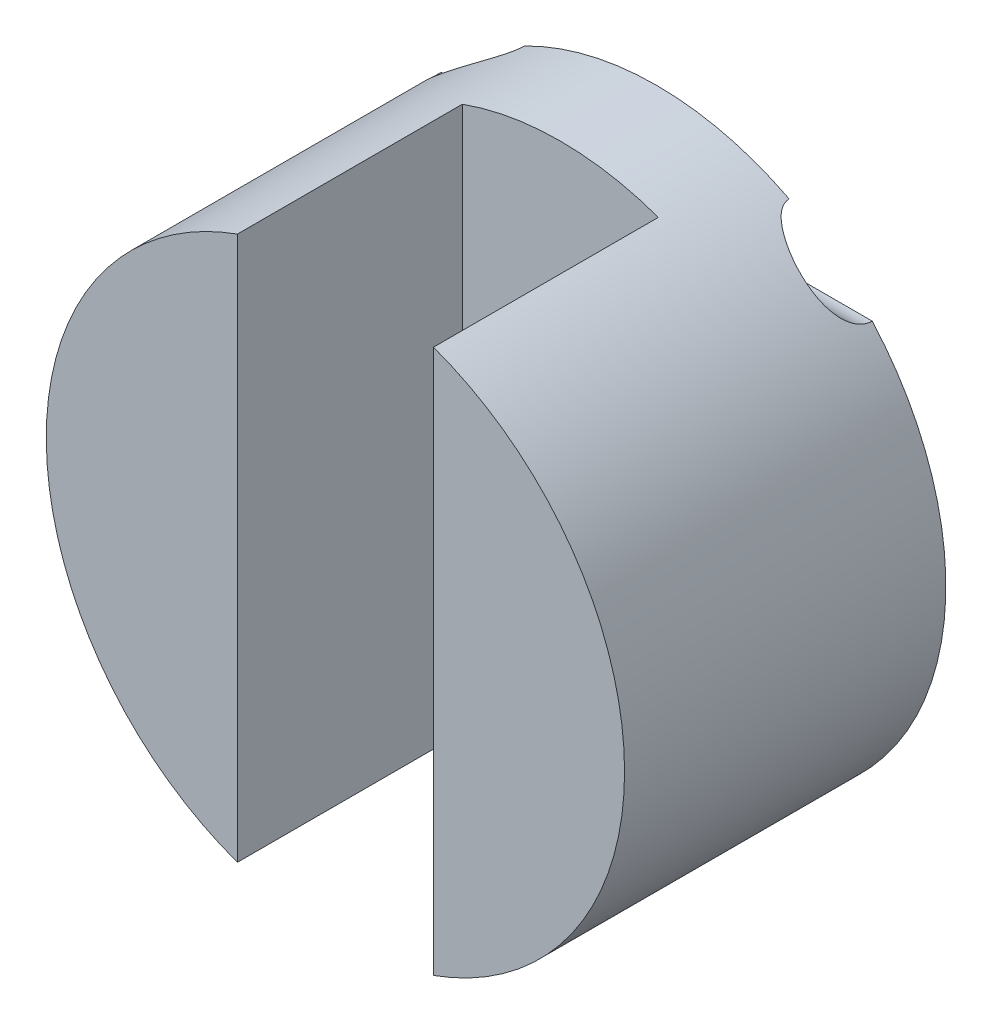
SolidWorks part; units mm, degrees
ref_plane "前视基准面" through (0, 0, 0) normal (0, 0, 1) x (1, 0, 0)
ref_plane "上视基准面" through (0, 0, 0) normal (0, 1, 0) x (1, 0, 0)
ref_plane "右视基准面" through (0, 0, 0) normal (1, 0, 0) x (0, 0, -1)
other "Configuration Table"
sketch "Sketch1" plane through (0, 0, 0) normal (0, 0, 1) x (1, 0, 0)
  circle A0 centre (0, 0) radius 90
extrude "Boss-Extrude1" add sketch "Sketch1" along normal blind 100
sketch "Sketch2" plane through (0, 0, 0) normal (0, 1, 0) x (1, 0, 0)
  line L1 (-30.5, -100) -> (30.5, -100)
  line L2 (-30.5, -100) -> (-30.5, -30)
  line L3 (-30.5, -30) -> (30.5, -30)
  line L4 (30.5, -100) -> (30.5, -30)
  line L5 (-30.5, -100) -> (30.5, -30) construction
  line L6 (-30.5, -30) -> (30.5, -100) construction
  point P0 (0, -65)
extrude "Cut-Extrude1" cut sketch "Sketch2" along normal blind 200 and the other way blind 200
sketch "Sketch3" plane through (0, 0, 0) normal (1, 0, 0) x (0, 0, -1)
  line L0 (0, -90) -> (0, 90) construction
  circle A0 centre (0, 70) radius 10
extrude "Cut-Extrude2" cut sketch "Sketch3" along normal blind 200 and the other way blind 200
ref_plane "bottom_contact_face" through (0, 0, 0) normal (0, 0, 1) x (1, 0, 0)
ref_plane "mid_plane_y" through (0, 0, 0) normal (0, 1, 0) x (1, 0, 0)
sketch3d "3DSketch1"
  line L0 (0, 0, 0) -> (0, 0, 100) construction
ref_axis "rotation_axis_z" through (0, 0, 0) along (0, 0, 1)
sketch3d "3DSketch2"
  line L0 (0, -100, 70) -> (0, 100, 70) construction
ref_axis "joint_axis_y" through (0, -100, 70) along (0, 1, 0)
